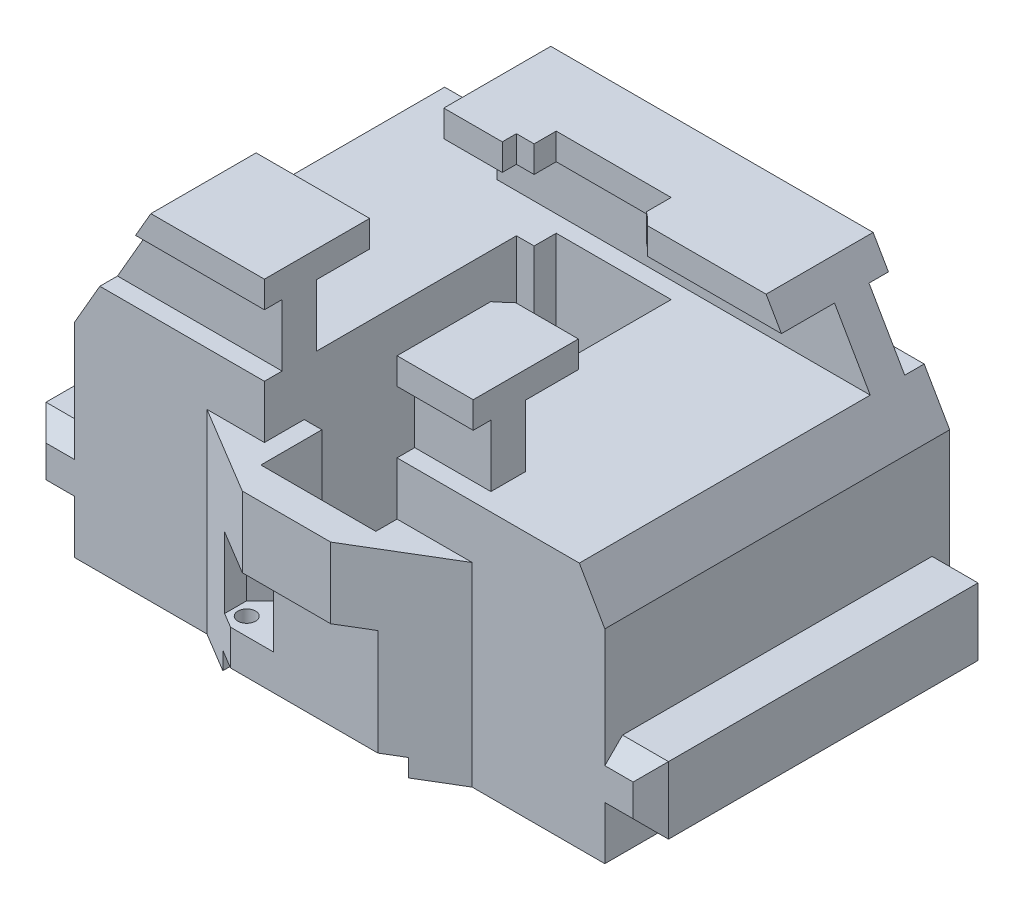
SolidWorks part; units mm, degrees
ref_plane "Front Plane" through (0, 0, 0) normal (0, 0, 1) x (1, 0, 0)
ref_plane "Top Plane" through (0, 0, 0) normal (0, 1, 0) x (1, 0, 0)
ref_plane "Right Plane" through (0, 0, 0) normal (1, 0, 0) x (0, 0, -1)
sketch "Sketch1" plane through (0, 0, 0) normal (0, 1, 0) x (1, 0, 0)
  line L1 (-60, 45) -> (0, 45)
  line L2 (-60, 45) -> (-60, 0)
  line L3 (-60, 0) -> (0, 0)
  line L4 (0, 45) -> (0, 0)
  dimension "D1" = 60
  dimension "D2" = 45
extrude "Boss-Extrude1" add sketch "Sketch1" along normal blind 30
sketch "Sketch2" plane through (0, 0, 0) normal (0, -1, 0) x (-1, 0, 0)
  line L0 (60, 45) -> (60, 0) construction
  line L1 (50.75, 13) -> (44.25, 13)
  line L2 (50.75, 13) -> (50.75, 29)
  line L3 (50.75, 29) -> (44.25, 29)
  line L4 (44.25, 13) -> (44.25, 29)
  line L5 (16.25, 13) -> (9.75, 13)
  line L6 (16.25, 13) -> (16.25, 29)
  line L7 (16.25, 29) -> (9.75, 29)
  line L8 (9.75, 13) -> (9.75, 29)
  line L10 (0, 0) -> (0, 45) construction
  line L12 (0, 45) -> (60, 45) construction
  dimension "D1" = 16
  dimension "D2" = 6.5
  dimension "D3" = 9.25
  dimension "D4" = 6.5
  dimension "D5" = 16
  dimension "D6" = 9.75
  dimension "D7" = 16
extrude "Cut-Extrude1" cut sketch "Sketch2" against normal blind 20
chamfer "Chamfer1" distance 5 angle 5 4 edges at (-16.25, 20, -21) (-9.75, 20, -21) (-50.75, 20, -21) (-44.25, 20, -21) first distance on face at (-16.25, 10, -21) first distance on face at (-9.75, 10, -21) first distance on face at (-50.75, 10, -21) first distance on face at (-44.25, 10, -21)
chamfer "Chamfer2" distance 5 angle 50 4 edges at (-47.5, 20, -29) (-13, 20, -29) (-13, 20, -13) (-47.5, 20, -13) first distance on face at (-47.5, 11.6667, -29) first distance on face at (-13, 11.6667, -29) first distance on face at (-13, 11.6667, -13) first distance on face at (-47.5, 11.6667, -13)
sketch "Sketch4" plane through (0, 0, -45) normal (0, 0, -1) x (-1, 0, 0)
  line L0 (11.5, 0) -> (28.3, 0)
  line L1 (0, 0) -> (60, 0) construction
  arc A0 (28.3, 0) -> (42.6119, 6.1301) centre (38.1836, -3.3031) cw
  arc A1 (42.6119, 6.1301) -> (46.2306, 12.0745) centre (44.0992, 9.2984) ccw
  arc A2 (46.2306, 12.0745) -> (11.5, 0) centre (32.8331, -5.3756) ccw
  dimension "D3" = 3.5
  dimension "D4" = 10.4209
  dimension "D7" = 22
  dimension "D1" = 16.8
  dimension "D2" = 11.5
  dimension "D5" = 3.3031
  dimension "D6" = 9.2984
extrude "Cut-Extrude2" cut sketch "Sketch4" against normal blind 10
chamfer "Chamfer3" distance 3 distance2 1.5 8 edges at (-13, 0, -13) (-9.75, 0, -21) (-13, 0, -29) (-16.25, 0, -21) (-47.5, 0, -29) (-44.25, 0, -21) (-47.5, 0, -13) (-50.75, 0, -21) first distance on face at (-47.5, 0, -21)
sketch "Sketch5" plane through (-60, 0, 0) normal (-1, 0, 0) x (0, 0, 1)
  line L0 (0, 30) -> (0, 0) construction
  line L1 (-45, 30) -> (0, 30)
  line L2 (-45, 30) -> (-45, 22)
  line L4 (0, 30) -> (0, 0)
  line L5 (-45, 22) -> (-6, 22)
  line L6 (-6, 22) -> (-6, 0)
  line L7 (-45, 0) -> (0, 0) construction
  line L8 (-6, 0) -> (0, 0)
  dimension "D1" = 8
extrude "Cut-Extrude3" cut sketch "Sketch5" against normal up to next
sketch "Sketch6" plane through (0, 0, 0) normal (0, -1, 0) x (-1, 0, 0)
  line L1 (44.25, 37) -> (16.25, 37)
  line L2 (44.25, 37) -> (44.25, 6)
  line L3 (44.25, 6) -> (16.25, 6)
  line L4 (16.25, 37) -> (16.25, 6)
  line L5 (44.25, 29) -> (44.25, 13) construction
  line L6 (0, 6) -> (60, 6) construction
  line L7 (16.25, 13) -> (16.25, 29) construction
  dimension "D1" = 31
extrude "Cut-Extrude4" cut sketch "Sketch6" against normal blind 1
sketch "Sketch12" plane through (0, 0, 0) normal (0, -1, 0) x (1, 0, 0)
  line L0 (-45, -6) -> (-35, 0)
  line L1 (-44.25, -6) -> (-60, -6) construction
  line L2 (-35, 0) -> (-25, 0)
  line L3 (-25, 0) -> (-15, -6)
  line L4 (-15, -6) -> (-45, -6)
  dimension "D1" = 30
  dimension "D2" = 15
  dimension "D3" = 6
  dimension "D4" = 10
  dimension "D5" = 10
extrude "Boss-Extrude2" add sketch "Sketch12" against normal up to surface (22 mm away) up to face at (-30, 22, -25.5)
sketch "Sketch7" plane through (0, 22, 0) normal (0, 1, 0) x (1, 0, 0)
  line L1 (-23.5, 8.6) -> (-36.5, 8.6)
  line L2 (-23.5, 8.6) -> (-23.5, 32)
  line L3 (-23.5, 32) -> (-36.5, 32)
  line L4 (-36.5, 8.6) -> (-36.5, 32)
  line L6 (0, 45) -> (-60, 45) construction
  line L9 (0, 6) -> (0, 45) construction
  circle A0 centre (-30, 25.5) radius 1.6355 construction
  dimension "D5" = 3.2709
  dimension "D1" = 13
  dimension "D2" = 23.5
  dimension "D3" = 19.5
  dimension "D4" = 30
  dimension "D6" = 16.9
  dimension "D7" = 6.5
extrude "Cut-Extrude5" cut sketch "Sketch7" against normal up to next
sketch "Sketch8" plane through (0, 1, 0) normal (0, -1, 0) x (1, 0, 0)
  line L1 (-36.5, -8.6) -> (-23.5, -8.6)
  line L2 (-36.5, -8.6) -> (-36.5, -3.6)
  line L3 (-36.5, -3.6) -> (-23.5, -3.6)
  line L4 (-23.5, -8.6) -> (-23.5, -3.6)
  line L5 (-36.5, -8.6) -> (-36.5, -32) construction
  line L6 (-23.5, -32) -> (-36.5, -32)
  line L7 (-23.5, -32) -> (-23.5, -37)
  line L8 (-23.5, -37) -> (-36.5, -37)
  line L9 (-36.5, -32) -> (-36.5, -37)
  line L10 (-23.5, -32) -> (-23.5, -8.6) construction
  dimension "D1" = 5
  dimension "D2" = 5
extrude "Cut-Extrude6" cut sketch "Sketch8" against normal up to next from offset 15.6 offset against normal yes
sketch "Sketch10" plane through (0, 22, 0) normal (0, 1, 0) x (1, 0, 0)
  line L0 (-27.5, 32) -> (-27.5, 34.5)
  line L1 (-23.5, 32) -> (-36.5, 32) construction
  line L2 (-27.5, 34.5) -> (-38.5, 34.5)
  line L3 (-38.5, 34.5) -> (-38.5, 10.5)
  line L4 (-38.5, 10.5) -> (-36.5, 10.5)
  line L5 (-36.5, 37) -> (-36.5, 3.6) construction
  line L6 (-36.5, 10.5) -> (-36.5, 32)
  line L7 (-36.5, 32) -> (-27.5, 32)
  dimension "D1" = 2.5
  dimension "D2" = 9
  dimension "D3" = 11
  dimension "D4" = 24
extrude "Cut-Extrude7" cut sketch "Sketch10" against normal up to next
sketch "Sketch13" plane through (0, 22, 0) normal (0, 1, 0) x (1, 0, 0)
  line L0 (-60, 45) -> (0, 45)
  line L1 (0, 45) -> (0, 6)
  line L2 (0, 6) -> (-15, 6)
  line L3 (-15, 6) -> (-23.5, 6)
  line L4 (-23.5, 3.6) -> (-23.5, 37) construction
  line L5 (-23.5, 6) -> (-23.5, 37)
  line L6 (-23.5, 37) -> (-36.5, 37)
  line L7 (-36.5, 37) -> (-36.5, 34.5)
  line L8 (-36.5, 34.5) -> (-38.5, 34.5)
  line L9 (-38.5, 34.5) -> (-38.5, 6)
  line L10 (-38.5, 6) -> (-60, 6)
  line L11 (-60, 6) -> (-60, 45)
extrude "Boss-Extrude3" add sketch "Sketch13" along normal blind 16
chamfer "Chamfer6" distance 15 angle 30 2 edges at (-60, 38, -25.5) (0, 38, -25.5) first distance on face at (-60, 19, -25.5) first distance on face at (0, 19, -25.5)
sketch "Sketch14" plane through (0, 38, 0) normal (0, 1, 0) x (1, 0, 0)
  line L0 (-38.5, 6) -> (-38.5, 34.5) construction
  line L1 (-36.5, 37) -> (-23.5, 37) construction
  circle A0 centre (-30.1, 25.4) radius 11
  dimension "D1" = 22
  dimension "D2" = 8.4
  dimension "D3" = 11.6
extrude "Cut-Extrude8" cut sketch "Sketch14" against normal blind 10
sketch "Sketch15" plane through (0, 38, 0) normal (0, 1, 0) x (1, 0, 0)
  line L1 (-65.1, 32.9) -> (4.9, 32.9)
  line L2 (-65.1, 32.9) -> (-65.1, 17.9)
  line L3 (-65.1, 17.9) -> (4.9, 17.9)
  line L4 (4.9, 32.9) -> (4.9, 17.9)
  arc A0 (-23.5, 16.6) -> (-23.5, 34.2) centre (-30.1, 25.4) ccw construction
  dimension "D1" = 15
  dimension "D2" = 7.5
  dimension "D3" = 70
  dimension "D4" = 35
extrude "Cut-Extrude9" cut sketch "Sketch15" against normal up to surface (10 mm away) up to face at (-39.8, 28, -25.4)
sketch "Sketch16" plane through (-38.5, 0, 0) normal (1, 0, 0) x (0, 0, -1)
  line L0 (6, 38) -> (6, 22) construction
  line L1 (17.9, 28) -> (11.9, 28)
  line L2 (17.9, 28) -> (17.9, 35)
  line L3 (17.9, 35) -> (11.9, 35)
  line L4 (11.9, 28) -> (11.9, 35)
  line L5 (6, 28) -> (8, 28)
  line L6 (6, 28) -> (6, 35)
  line L7 (6, 35) -> (8, 35)
  line L8 (8, 28) -> (8, 35)
  dimension "D1" = 2
  dimension "D2" = 6
  dimension "D3" = 7
  dimension "D4" = 7
extrude "Cut-Extrude10" cut sketch "Sketch16" against normal through all both and the other way through all
sketch "Sketch17" plane through (-38.5, 0, 0) normal (1, 0, 0) x (0, 0, -1)
  line L0 (45, 23) -> (45, 38) construction
  line L1 (32.9, 28) -> (38.9, 28)
  line L2 (32.9, 28) -> (32.9, 35)
  line L3 (32.9, 35) -> (38.9, 35)
  line L4 (38.9, 28) -> (38.9, 35)
  line L5 (45, 28) -> (42.8, 28)
  line L6 (45, 28) -> (45, 35)
  line L7 (45, 35) -> (42.8, 35)
  line L8 (42.8, 28) -> (42.8, 35)
  dimension "D1" = 7
  dimension "D2" = 6
  dimension "D3" = 3.9
extrude "Cut-Extrude11" cut sketch "Sketch17" against normal through all both and the other way through all
sketch "Sketch18" plane through (0, 0, 0) normal (0, -1, 0) x (1, 0, 0)
  line L1 (-40.5, 2) -> (-19.5, 2)
  line L2 (-40.5, 2) -> (-40.5, -6)
  line L3 (-40.5, -6) -> (-19.5, -6)
  line L4 (-19.5, 2) -> (-19.5, -6)
  dimension "D1" = 21
  dimension "D2" = 4.5
  dimension "D3" = 8
  dimension "D4" = 0
extrude "Cut-Extrude12" cut sketch "Sketch18" against normal blind 2
sketch "Sketch19" plane through (0, 2, 0) normal (0, -1, 0) x (1, 0, 0)
  line L0 (-40.5, -3.3) -> (-40.5, -6) construction
  line L1 (-19.5, -6) -> (-40.5, -6) construction
  line L2 (-35, 0) -> (-25, 0) construction
  line L3 (-39.1705, 3.1892) -> (-20.8295, 3.1892)
  line L4 (-39.1705, 3.1892) -> (-39.1705, -2)
  line L5 (-39.1705, -2) -> (-20.8295, -2)
  line L6 (-20.8295, 3.1892) -> (-20.8295, -2)
  circle A0 centre (-38.5, -4) radius 1
  circle A1 centre (-22.5, -4) radius 1
  dimension "D1" = 2
  dimension "D2" = 16
  dimension "D3" = 2
  dimension "D4" = 2
  dimension "D5" = 2
extrude "Cut-Extrude13" cut sketch "Sketch19" against normal blind 12
sketch "Sketch20" plane through (0, 0, -10.5) normal (0, 0, -1) x (-1, 0, 0)
  line L0 (38.5, 1) -> (38.5, 22) construction
  line L1 (38.5, 14) -> (36.5, 14)
  line L2 (38.5, 14) -> (38.5, 6)
  line L3 (38.5, 6) -> (36.5, 6)
  line L4 (36.5, 14) -> (36.5, 6)
  line L5 (36.5, 1) -> (36.5, 22) construction
  line L6 (36.5, 1) -> (38.5, 1) construction
  point P10 (37.5, 1)
  dimension "D1" = 5
  dimension "D2" = 8
extrude "Cut-Extrude14" cut sketch "Sketch20" against normal up to next
sketch "Sketch21" plane through (0, 38, 0) normal (0, 1, 0) x (1, 0, 0)
  line L0 (-2.8868, 6) -> (-2.8868, 8) construction
  line L1 (-61.9141, 51.6985) -> (-45.1132, 51.6985)
  line L2 (-61.9141, 51.6985) -> (-61.9141, 28.5299)
  line L3 (-61.9141, 28.5299) -> (-45.1132, 28.5299)
  line L4 (-45.1132, 51.6985) -> (-45.1132, 28.5299)
  line L5 (10.427, -5.5418) -> (-14.8868, -5.5418)
  line L6 (10.427, -5.5418) -> (10.427, 21.7171)
  line L7 (10.427, 21.7171) -> (-14.8868, 21.7171)
  line L8 (-14.8868, -5.5418) -> (-14.8868, 21.7171)
  dimension "D1" = 12
  dimension "D2" = 12
extrude "Cut-Extrude15" cut sketch "Sketch21" against normal up to surface (10 mm away) up to face at (-30, 28, -43.9)
sketch "Sketch22" plane through (0, 0, -45) normal (0, 0, -1) x (-1, 0, 0)
  line L0 (0, 23) -> (0, 0) construction
  line L1 (0, 4) -> (-5.2, 4)
  line L2 (0, 4) -> (0, 11.6)
  line L3 (0, 11.6) -> (-5.2, 11.6)
  line L4 (-5.2, 4) -> (-5.2, 11.6)
  line L5 (60, 23) -> (60, 0) construction
  line L6 (60, 4) -> (65.2, 4)
  line L7 (60, 4) -> (60, 11.6)
  line L8 (60, 11.6) -> (65.2, 11.6)
  line L9 (65.2, 4) -> (65.2, 11.6)
  dimension "D1" = 4
  dimension "D2" = 7.6
  dimension "D3" = 5.2
  dimension "D4" = 5.2
  dimension "D5" = 7.6
extrude "Boss-Extrude4" add sketch "Sketch22" against normal up to surface (39 mm away) up to face at (-49.159, 17.5714, -6)
chamfer "Chamfer7" distance 2 angle 45 12 edges at (2.6, 11.6, -45) (5.2, 7.8, -45) (2.6, 4, -45) (-62.6, 4, -45) (-65.2, 7.8, -45) (-62.6, 11.6, -45) (-62.6, 11.6, -6) (-62.6, 4, -6) (-65.2, 7.8, -6) (2.6, 4, -6) (5.2, 7.8, -6) (2.6, 11.6, -6)
sketch "Sketch23" plane through (0, 0, -2) normal (0, 0, 1) x (1, 0, 0)
  line L0 (-38.3333, 6) -> (-36.5, 6) construction
  line L1 (-40, 14) -> (-33.5, 14)
  line L2 (-40, 14) -> (-40, 6)
  line L3 (-40, 6) -> (-33.5, 6)
  line L4 (-33.5, 14) -> (-33.5, 6)
  line L5 (-36.5, 6) -> (-36.5, 14) construction
  dimension "D1" = 6.5
  dimension "D2" = 3
extrude "Cut-Extrude16" cut sketch "Sketch23" against normal blind 3
chamfer "Chamfer8" distance 2 angle 45 2 edges at (-36.5, 10, -5) (-38.5, 10, -5)
equation "\"D2@Sketch12\"=(60-\"D1@Sketch12\")/2"
equation "\"D5@Sketch12\"=(\"D1@Sketch12\"-\"D4@Sketch12\")/2"
equation "\"D2@Sketch15\"=\"D1@Sketch15\"/2"
equation "\"D4@Sketch16\"=\"D3@Sketch16\""
equation "\"D2@Sketch18\"=(30-\"D1@Sketch18\")/2"
equation "\"D3@Sketch19\"=(20-\"D2@Sketch19\")/2"
equation "\"D4@Sketch19\"=\"D3@Sketch19\""
equation "\"D5@Sketch22\"=\"D2@Sketch22\""
equation "\"D4@Sketch22\"=\"D3@Sketch22\""
